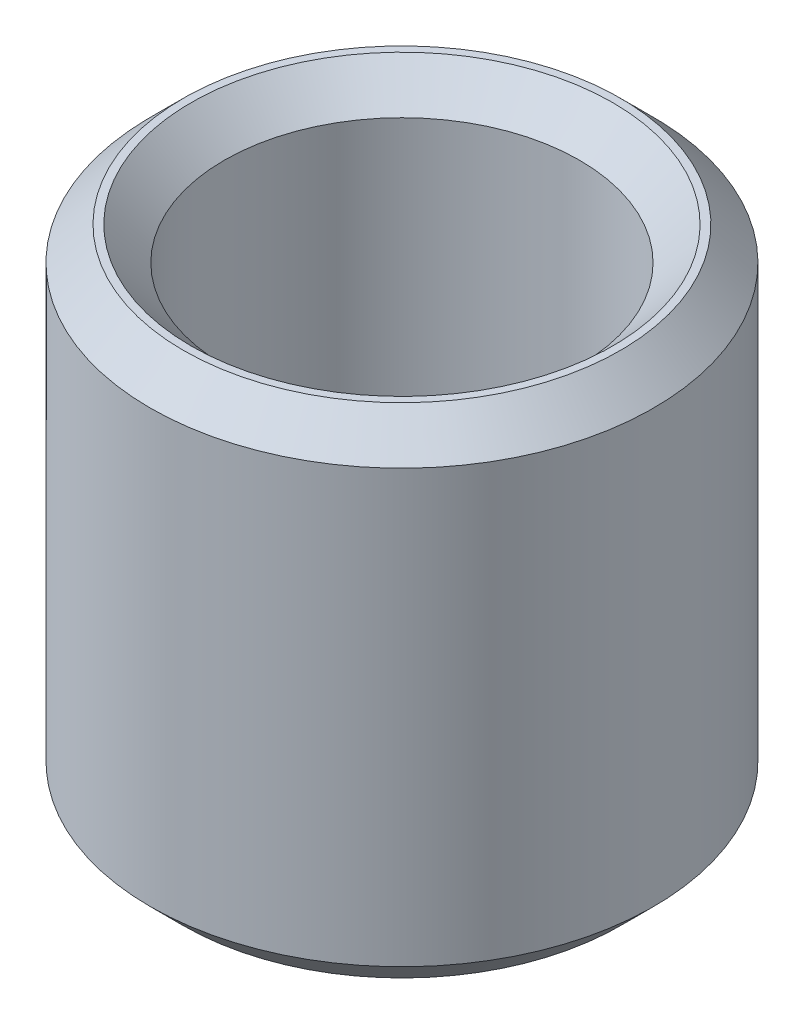
SolidWorks part; units mm, degrees
ref_plane "Front Plane" through (0, 0, 0) normal (0, 0, 1) x (1, 0, 0)
ref_plane "Top Plane" through (0, 0, 0) normal (0, 1, 0) x (1, 0, 0)
ref_plane "Right Plane" through (0, 0, 0) normal (1, 0, 0) x (0, 0, -1)
sketch "Sketch1" plane through (0, 0, 0) normal (0, 1, 0) x (1, 0, 0)
  circle A0 centre (0, 0) radius 20
  dimension "SLEEVE_OD" = 40
extrude "Boss-Extrude1" add sketch "Sketch1" along normal blind 39.5851
sketch "Sketch2" plane through (0, 0, 0) normal (0, 1, 0) x (1, 0, 0)
  circle A0 centre (0, 0) radius 14.1093
  dimension "BORE_D" = 28.2186
extrude "Cut-Extrude1" cut sketch "Sketch2" along normal through all
chamfer "Chamfer1" distance 2.6412 angle 45 4 edges at (0, 39.5851, 14.1093) (0, 0, 14.1093) (0, 0, 20) (0, 39.5851, 20)
